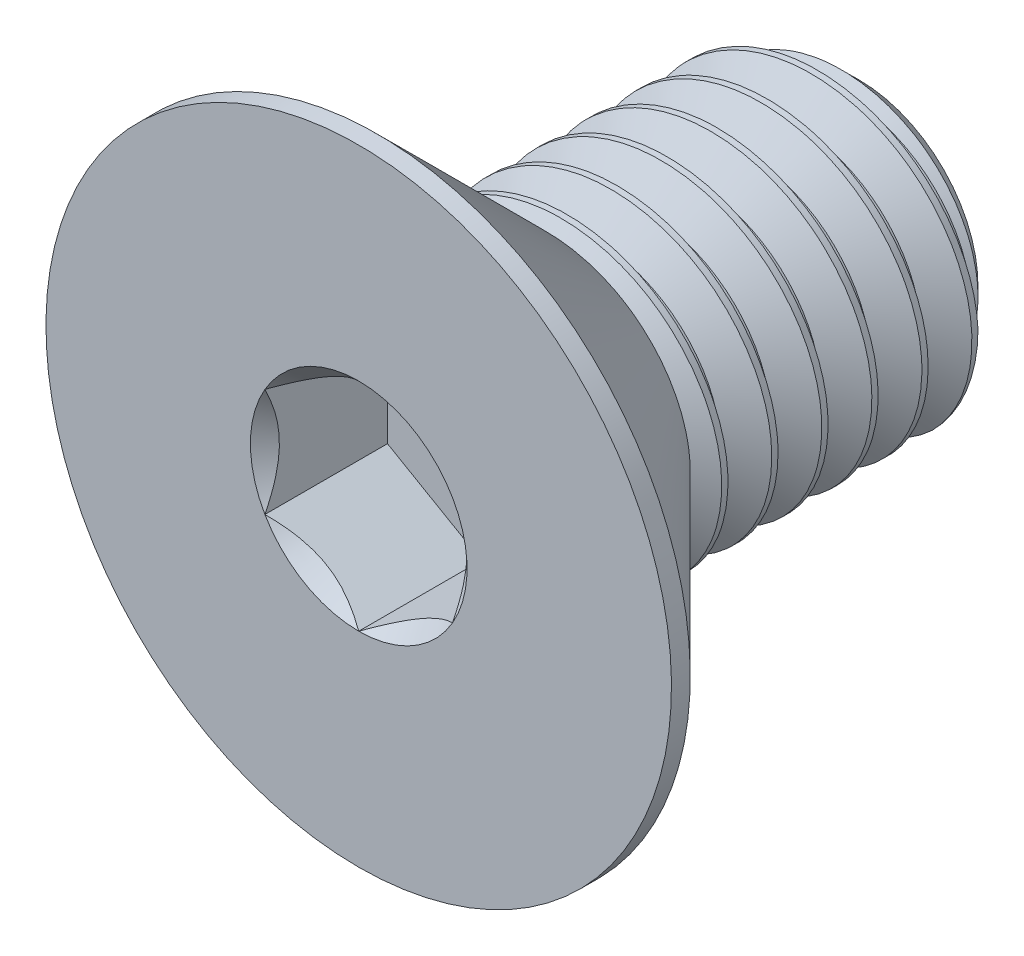
SolidWorks part; units mm, degrees
ref_plane "Front" through (0, 0, 0) normal (0, 0, 1) x (1, 0, 0)
ref_plane "Top" through (0, 0, 0) normal (0, 1, 0) x (1, 0, 0)
ref_plane "Right" through (0, 0, 0) normal (1, 0, 0) x (0, 0, -1)
sketch "Sketch1" plane through (0, 0, 0) normal (1, 0, 0) x (0, 0, -1)
  line L0 (0, 5) -> (0.3, 5) construction
  line L1 (0.3, 5) -> (2.8, 2.5) construction
  line L2 (0, 2.5) -> (8, 2.5)
  line L3 (8, 2.5) -> (8, 0)
  line L4 (8, 0) -> (0, 0)
  line L5 (0, 0) -> (0, 5) construction
  line L6 (0, 5) -> (0, -5) construction
  line L7 (8, 2.5) -> (8, -2.5) construction
  line L8 (0, -5) -> (0.3, -5) construction
  line L9 (0.3, -5) -> (2.8, -2.5) construction
  line L11 (0, 2.5) -> (0, 0)
  line L12 (2.8, 2.5) -> (2.8, 0) construction
  dimension "Head Ht" = 2.8
  dimension "Head Dia" = 10
  dimension "Dia" = 5
  dimension "Lg" = 8
  dimension "Head Angle" = 90
revolve "Revolve1" add sketch "Sketch1" angle 360 mid plane about L4
sketch "Sketch3" plane through (0, 0, -8) normal (0, 0, -1) x (-1, 0, 0)
  circle A0 centre (0, 0) radius 2.5
curve "Helix/Spiral1" pitch 0.8 height 8 radius 2.5 centre (0, 0, -8) axis (0, 0, 1) start towards (0, 1, 0)
sketch "Sketch2" plane through (0, 0, 0) normal (1, 0, 0) x (0, 0, -1)
  line L0 (8, 2.5) -> (8.7, 2.5)
  line L1 (8.7, 2.5) -> (8.4, 1.9804)
  line L2 (8.4, 1.9804) -> (8.3, 1.9804)
  line L3 (8.3, 1.9804) -> (8, 2.5)
  line L4 (8.15, 2.2402) -> (8.55, 2.2402) construction
  dimension "D1" = 60
  dimension "D2" = 0.1
  dimension "D3" = 0.4
chamfer "Chamfer1" distance 0.6 angle 45 1 edges at (0, 2.5, -8)
sweep "Cut-Sweep1" cut profiles "Sketch2" path "Helix/Spiral1" align with end faces yes
sketch "Sketch7" plane through (0, 0, 0) normal (1, 0, 0) x (0, 0, -1)
  line L0 (0, 5) -> (0.3, 5) construction
  line L1 (0.3, 5) -> (2.8, 2.5) construction
  line L2 (0, 5) -> (0.3, 5)
  line L3 (0.3, 5) -> (2.8, 2.5)
  line L4 (2.8, 2.5) -> (2.8, 0) construction
  line L5 (2.8, 2.5) -> (2.8, 0)
  line L7 (0, 0) -> (0, 5) construction
  line L8 (0, 0) -> (0, 5)
  line L9 (0, 0) -> (2.8, 0)
  line L10 (5.5, 0) -> (-5.5, 0) construction
revolve "Revolve2" add sketch "Sketch7" angle 360 mid plane about L9
ref_plane "Plane1" through (0, 0, -2.8) normal (0, 0, 1) x (1, 0, 0)
sketch "Sketch8" plane through (0, 0, -2.8) normal (0, 0, 1) x (1, 0, 0)
  circle A0 centre (0, 0) radius 2.5
extrude "Boss-Extrude1" add sketch "Sketch8" against normal through all draft 45
sketch "Sketch5" plane through (0, 0, 0) normal (0, 0, 1) x (1, 0, 0)
  line L1 (1.5, -0.866) -> (1.5, 0.866)
  line L2 (1.5, 0.866) -> (0, 1.7321)
  line L3 (0, 1.7321) -> (-1.5, 0.866)
  line L4 (-1.5, 0.866) -> (-1.5, -0.866)
  line L5 (-1.5, -0.866) -> (0, -1.7321)
  line L6 (0, -1.7321) -> (1.5, -0.866)
  circle A0 centre (0, 0) radius 1.5 construction
  dimension "Hex" = 3
extrude "Cut-Extrude2" cut sketch "Sketch5" against normal blind 1.96
sketch "Sketch6" plane through (0, 0, 0) normal (0, 0, 1) x (1, 0, 0)
  circle A0 centre (0, 0) radius 1.7321
extrude "Cut-Extrude3" cut sketch "Sketch6" against normal blind 1.96 draft 45
sketch "Sketch9" [suppressed] plane through (0, 0, -5.5) normal (0, 0, 1) x (1, 0, 0)
  circle A1 centre (0, 0) radius 5
  circle A2 centre (0, 0) radius 5
  point P0 (0, 5)
  dimension "D1" = 0
extrude "Boss-Extrude2" [suppressed] add sketch "Sketch9" against normal offset from surface (18.5 mm away) 26 up to face at (0, 1.9, -8)
fillet "Fillet1" [suppressed] radius 0.5
sketch "Sketch10" plane through (0, 0, 0) normal (1, 0, 0) x (0, 0, -1)
  line L0 (8, 2.5) -> (8, -2.5) construction
  point P0 (6.8, -2.5)
  dimension "D1" = 1.2
equation "\"D3@Helix/Spiral1\" = \"Lg@Sketch1\""
equation "\"D2@Sketch2\" = \"D4@Helix/Spiral1\" * .125"
equation "\"D3@Sketch2\" = \"D4@Helix/Spiral1\" * .5"
equation "\"D1@Chamfer1\" = \"D4@Helix/Spiral1\" * .75"
equation "\"D1@Cut-Extrude2\" = \"Head Ht@Sketch1\" * .7"
equation "\"D1@Sketch10\" = \"D4@Helix/Spiral1\" * 1.5"
equation "\"D1@Cut-Extrude3\" = \"D1@Cut-Extrude2\""
equation "\"D1@Fillet1\" = \"Dia@Sketch1\" * .1"
